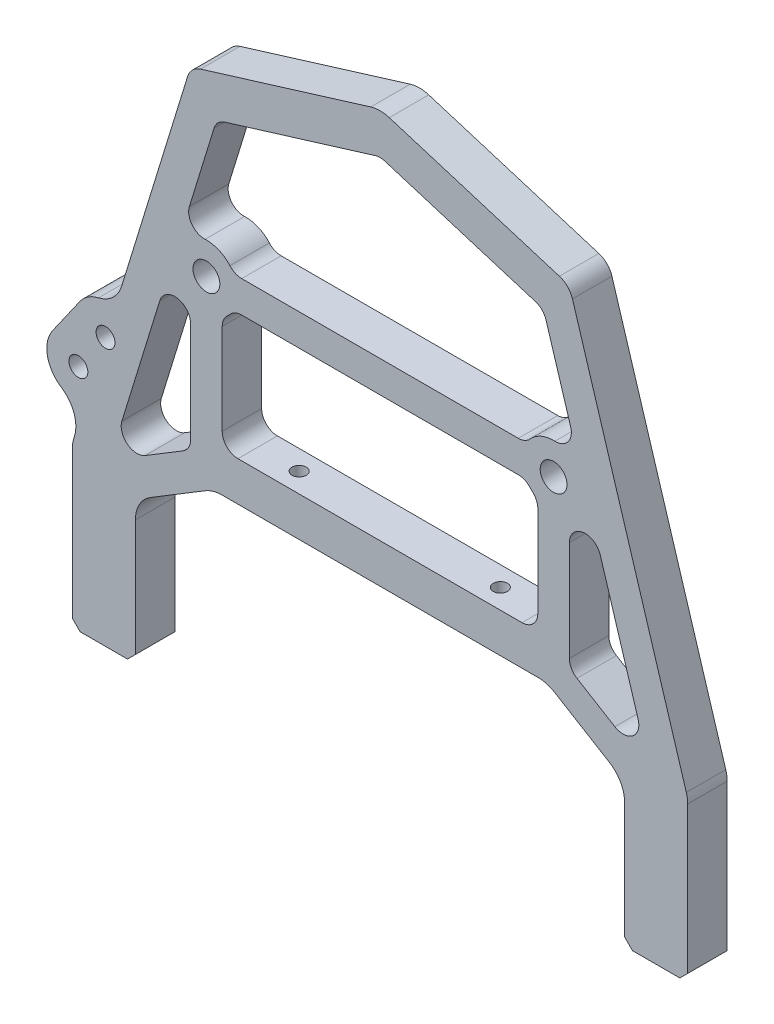
SolidWorks part; units mm, degrees
material "6061-T6 (SS)"
ref_plane "Front Plane" through (0, 0, 0) normal (0, 0, 1) x (1, 0, 0)
ref_plane "Top Plane" through (0, 0, 0) normal (0, 1, 0) x (1, 0, 0)
ref_plane "Right Plane" through (0, 0, 0) normal (1, 0, 0) x (0, 0, -1)
sketch "Sketch1" plane through (0, 0, 0) normal (0, 0, 1) x (1, 0, 0)
  line L0 (0, 0) -> (-39, 0) construction
  line L1 (0, 0) -> (0, 32.1567) construction
  line L2 (-35, 0) -> (-35, 19.1214) construction
  line L3 (-35, 19.1214) -> (-22, 27) construction
  line L4 (-22, 27) -> (-22, 47) construction
  line L6 (-22, 27) -> (22, 27) construction
  line L7 (-35, 19.1214) -> (-22, 47) construction
  line L11 (-31, 0) -> (-31, 18.0377)
  line L13 (-31, 18.0377) -> (-21.1619, 24)
  line L14 (-21.1619, 24) -> (21.1619, 24)
  line L15 (-20, 43.5359) -> (-20, 29)
  line L21 (35, 19.1214) -> (22, 27) construction
  line L22 (31, 18.0377) -> (21.1619, 24)
  line L23 (22, 27) -> (22, 47) construction
  line L25 (-31, 0) -> (-39, 0)
  line L29 (-39, 20.2052) -> (-24.3896, 67.7346)
  line L30 (-20, 29) -> (20, 29)
  line L32 (31, 0) -> (39, 0)
  line L33 (31, 0) -> (31, 18.0377)
  line L35 (39, 20.2052) -> (24.3896, 67.7346)
  line L37 (20, 43.5359) -> (20, 29)
  line L38 (-39, 0) -> (-39, 20.2052)
  line L39 (-31, 18.0377) -> (-39, 20.2052) construction
  line L40 (39, 0) -> (39, 20.2052)
  line L41 (-22, 47) -> (0, 47) construction
  line L42 (-18.5359, 45) -> (18.5359, 45)
  line L43 (-18.5359, 49) -> (18.5359, 49)
  line L44 (-22.7346, 69.3896) -> (0, 76.3782)
  line L45 (-22, 67) -> (0, 73.7627) construction
  line L46 (-20.7198, 64.7781) -> (-25.8234, 48.1753)
  line L47 (-20.7198, 64.7781) -> (0, 71.1473)
  line L48 (22.7346, 69.3896) -> (0, 76.3782)
  line L49 (20.7198, 64.7781) -> (0, 71.1473)
  line L50 (20.7198, 64.7781) -> (25.8234, 48.1753)
  arc A5 (-22.7346, 69.3896) -> (-24.3896, 67.7346) centre (-22, 67) ccw
  arc A12 (22.7346, 69.3896) -> (24.3896, 67.7346) centre (22, 67) cw
  circle A14 centre (-22, 47) radius 4
  circle A15 centre (22, 47) radius 4
  point P10 (0, 24)
  point P11 (0, 29)
  point P27 (-25.9697, 47.4917)
  point P28 (0, 27)
  point P40 (0, 29)
  point P48 (0, 45)
  point P51 (0, 49)
  dimension "D8" = 2.5
  dimension "D9" = 8
  dimension "D1" = 27
  dimension "D2" = 65
  dimension "D3" = 35
  dimension "D4" = 22
  dimension "D5" = 20
  dimension "D11" = 3
  dimension "D12" = 3
  dimension "D16" = 20
  dimension "D7" = 2
  dimension "D10" = 4
  dimension "D6" = 2
  dimension "D13" = 2
  dimension "D14" = 2
  dimension "D15" = 2.5
  dimension "D17" = 17.087
extrude "Boss-Extrude3" add sketch "Sketch1" along normal mid plane 5 contours L15 L25 L11 L13 L14 L22 | A14 | L42 A15 L43 A14 | A15 region at (-35, 1.0917, 0) region at (-22, 47, 0) region at (0, 47, 0) region at (22, 47, 0)
fillet "Fillet3" radius 2 13 edges at (20, 29, 0) (-20, 29, 0) (-18.5359, 45, 0) (-20, 43.5359, 0) (20, 43.5359, 0) (18.5359, 45, 0) (18.5359, 49, 0) (-18.5359, 49, 0) (-25.8234, 48.1753, 0) (-20.7198, 64.7781, 0) (0, 71.1473, 0) (20.7198, 64.7781, 0) (25.8234, 48.1753, 0)
sketch "Sketch2" plane through (0, 0, -2.5) normal (0, 0, -1) x (-1, 0, 0)
  line L0 (-34.2565, 20.7413) -> (-25.8234, 48.1753)
  line L1 (-24, 43.5359) -> (-24, 26.9572)
  line L2 (-24, 26.9572) -> (-34.2565, 20.7413)
  line L3 (-39, 20.2052) -> (-24.3896, 67.7346) construction
  line L4 (-20, 42.5279) -> (-20, 31) construction
  line L5 (-31, 18.0377) -> (-21.1619, 24) construction
  line L6 (0, 0) -> (0, 18.0631) construction
  line L10 (-21.0311, 63.7653) -> (-24.1613, 53.5825) construction
  line L11 (34.2565, 20.7413) -> (25.8234, 48.1753)
  line L12 (24, 26.9572) -> (34.2565, 20.7413)
  line L13 (24, 43.5359) -> (24, 26.9572)
  arc A3 (-25.8234, 48.1753) -> (-24, 43.5359) centre (-22, 47) ccw
  arc A4 (25.8234, 48.1753) -> (24, 43.5359) centre (22, 47) cw
  arc A5 (-27.9117, 41.3818) -> (-24, 40.7942) centre (-26, 40.7942) cw
  arc A6 (27.9117, 41.3818) -> (24, 40.7942) centre (26, 40.7942) ccw
  dimension "D3" = 2
  dimension "D1" = 4
  dimension "D2" = 4
extrude "Cut-Extrude1" cut sketch "Sketch2" against normal through all contours A5 L0 L2 L1 | L11 A6 L13 L12 region at (27.8167, 31.7443, -2.5) region at (-27.8167, 31.7443, -2.5)
fillet "Fillet1" radius 2 4 edges at (24, 26.9572, 0) (34.2565, 20.7413, 0) (-34.2565, 20.7413, 0) (-24, 26.9572, 0)
fillet "Fillet2" radius 4 7 edges at (-21.1619, 24, 0) (21.1619, 24, 0) (-31, 18.0377, 0) (31, 18.0377, 0) (-39, 20.2052, 0) (39, 20.2052, 0) (0, 76.3782, 0)
hole_wizard "M3 Clearance Hole1" positions "Sketch3" profile "Sketch4" hole size "M3" standard "ANSI Metric" end condition through all
sketch "Sketch3" plane through (0, 0, 2.5) normal (0, 0, 1) x (1, 0, 0)
  point P8 (-22, 47)
  point P11 (22, 47)
sketch "Sketch4" plane through (-22, 47, 2.5) normal (1, 0, 0) x (0, -1, 0)
  line L0 (0, 0) -> (0, 5)
  line L1 (0, 5) -> (1.7, 5)
  line L2 (1.7, 5) -> (1.7, 0)
  line L5 (1.7, 0) -> (0, 0)
  line L11 (0, -6.35) -> (0, 107.95) construction
  dimension "Thru Hole Dia." = 3.4
  dimension "Thru Hole Depth" = 5
hole_wizard "M3x0.5 Tapped Hole1" positions "Sketch7" profile "Sketch8" tap size "M3x0.5" standard "ANSI Metric"
sketch "Sketch7" plane through (0, 0, 0) normal (0, -1, 0) x (-1, 0, 0)
  line L0 (0, 0) -> (0, 9.7469) construction
  line L2 (-35, 2.5) -> (-35, 6.9037) construction
  line L3 (-31, 2.5) -> (-39, 2.5) construction
  point P0 (-35, 0)
  point P16 (35, 0)
sketch "Sketch8" plane through (35, 0, 0) normal (1, 0, 0) x (0, 0, -1)
  line L0 (0, 0) -> (0, 8.2511)
  line L1 (0, 8.2511) -> (1.25, 7.5)
  line L2 (1.25, 7.5) -> (1.25, 0)
  line L5 (1.25, 0) -> (0, 0)
  line L10 (0, 8.2511) -> (-1.25, 7.5) construction
  line L11 (0, -6.35) -> (0, 107.95) construction
  dimension "Tap Drill Dia." = 2.5
  dimension "Tap Drill Depth" = 7.5
  dimension "Drill Angle" = 118
cosmetic thread "Hole Thread1" parameters "D1"=6, "D2"=3
cosmetic thread "Hole Thread2" parameters "D1"=6, "D2"=3
chamfer "Chamfer1" distance 1 angle 45 4 edges at (-31, 0, 0) (31, 0, 0) (-39, 0, 0) (39, 0, 0)
hole_wizard "CBORE for M1.6 SHCS1" positions "Sketch9" profile "Sketch11" counterbore size "M1.6" standard "ANSI Metric" end condition up to next
sketch "Sketch9" plane through (0, 24, 0) normal (0, -1, 0) x (-1, 0, 0)
  point P10 (12.75, 0)
  point P13 (-12.75, 0)
sketch "Sketch11" plane through (-12.75, 24, 0) normal (1, 0, 0) x (0, 0, -1)
  line L0 (0, 0) -> (0, 5)
  line L1 (0, 5) -> (0.9, 5)
  line L3 (0.9, 5) -> (0.9, 1.6)
  line L4 (0.9, 1.6) -> (1.75, 1.6)
  line L5 (1.75, 1.6) -> (1.75, 0)
  line L7 (1.75, 0) -> (0, 0)
  line L11 (0, -6.35) -> (0, 107.95) construction
  dimension "Thru Hole Dia." = 1.8
  dimension "Thru Hole Depth" = 5
  dimension "C'Bore Dia." = 3.5
  dimension "C'Bore Depth" = 1.6
sketch "Sketch12" plane through (0, 0, 2.5) normal (0, 0, 1) x (1, 0, 0)
  line L0 (-18, 29) -> (18, 29) construction
  line L2 (-38.2271, 29) -> (-34.7857, 33.9149) construction
  line L3 (-41.5037, 31.2943) -> (-38.0623, 36.2092)
  line L4 (-38.2271, 29) -> (-34.7857, 33.9149) construction
  line L5 (0, 0) -> (-23.3136, 0) construction
  line L6 (-34.9505, 26.7057) -> (-31.5091, 31.6206)
  line L7 (-38.8234, 20.7796) -> (-24.3896, 67.7346) construction
  arc A0 (-41.5037, 31.2943) -> (-34.9505, 26.7057) centre (-38.2271, 29) ccw
  arc A1 (-31.5091, 31.6206) -> (-38.0623, 36.2092) centre (-34.7857, 33.9149) ccw
  point P0 (0, 0)
  point P5 (-36.5064, 31.4575)
  dimension "D3" = 4
  dimension "D1" = 6
  dimension "D2" = 125
extrude "Boss-Extrude4" add sketch "Sketch12" against normal up to surface (5 mm away) contours L6 A1 L3 A0 up to face at (-20.3, 47, -2.5)
fillet "Fillet4" radius 4 2 edges at (-37.5059, 25.0656, 0) (-33.6104, 37.7383, 0)
hole_wizard "M2 Clearance Hole1" positions "Sketch13" profile "Sketch15" hole size "M2" standard "ANSI Metric"
sketch "Sketch13" plane through (0, 0, 2.5) normal (0, 0, 1) x (1, 0, 0)
  point P0 (-38.2271, 29)
  point P3 (-34.7857, 33.9149)
sketch "Sketch15" plane through (-38.2271, 29, 2.5) normal (1, 0, 0) x (0, -1, 0)
  line L0 (0, 0) -> (0, 8.221)
  line L1 (0, 8.221) -> (1.2, 7.5)
  line L2 (1.2, 7.5) -> (1.2, 0)
  line L5 (1.2, 0) -> (0, 0)
  line L10 (0, 8.221) -> (-1.2, 7.5) construction
  line L11 (0, -6.35) -> (0, 107.95) construction
  dimension "Hole Dia." = 2.4
  dimension "Hole Depth" = 7.5
  dimension "Drill Angle" = 118
equation "\"D12@Sketch1\"=\"D11@Sketch1\""
equation "\"D15@Sketch1\"=\"D8@Sketch1\""
